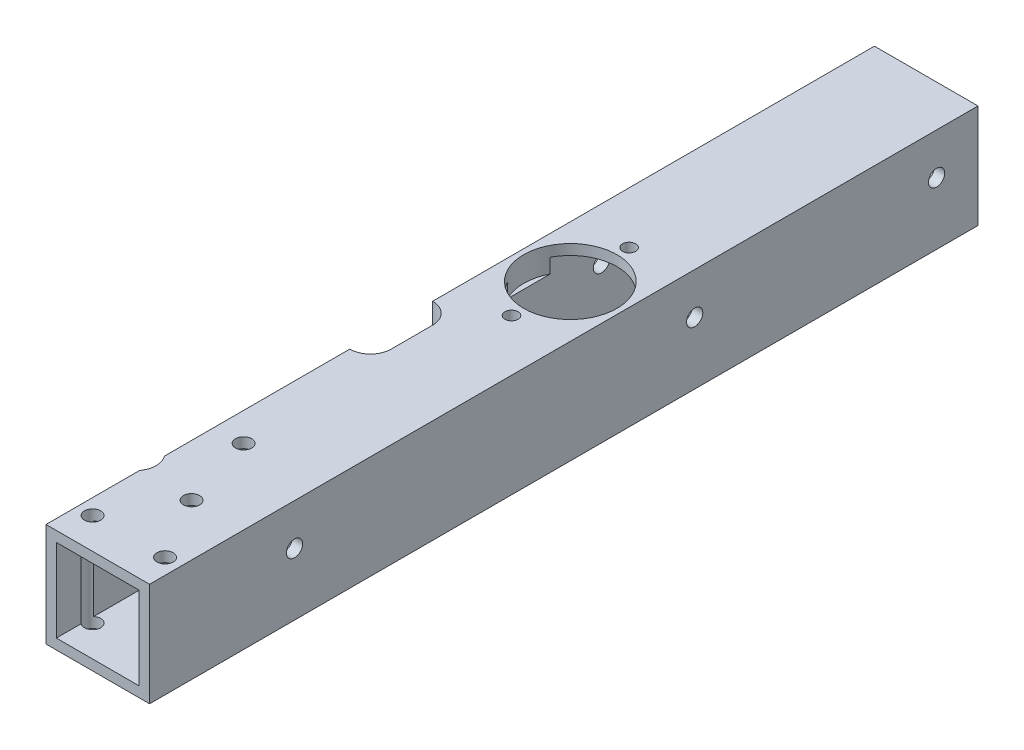
SolidWorks part; units mm, degrees
material "6061 Alloy"
ref_plane "Front Plane" through (0, 0, 0) normal (0, 0, 1) x (1, 0, 0)
ref_plane "Top Plane" through (0, 0, 0) normal (0, 1, 0) x (1, 0, 0)
ref_plane "Right Plane" through (0, 0, 0) normal (1, 0, 0) x (0, 0, -1)
sketch "Sketch1" plane through (0, 0, 0) normal (0, 0, 1) x (1, 0, 0)
  line L0 (-12.7, 12.7) -> (12.7, 12.7)
  line L2 (-15.875, 15.875) -> (15.875, 15.875)
  line L3 (-15.875, 15.875) -> (-15.875, -15.875)
  line L4 (-15.875, -15.875) -> (15.875, -15.875)
  line L5 (15.875, 15.875) -> (15.875, -15.875)
  line L10 (12.7, 12.7) -> (12.7, -12.7)
  line L11 (-12.7, -12.7) -> (12.7, -12.7)
  line L12 (-12.7, 12.7) -> (-12.7, -12.7)
  point P12 (0, 15.875)
  point P14 (15.875, 0)
  dimension "Wall Thickness" = 3.175
  dimension "Outside Width" = 31.75
  dimension "Outside Height" = 31.75
  dimension "Inside Height" = 25.4
  dimension "Inside Width" = 25.4
sketch "Sketch2" plane through (0, 0, 0) normal (1, 0, 0) x (0, 0, -1)
  line L0 (127, 0) -> (-127, 0)
  point P4 (0, 0)
  point P7 (-127, 0)
  point P10 (127, 0)
  dimension "Length" = 254
sketch "Sketch3" plane through (0, 0, 0) normal (0, 0, 1) x (1, 0, 0)
  line L21 (15.875, 15.875) -> (-15.875, 15.875)
  line L22 (15.875, -15.875) -> (15.875, 15.875)
  line L23 (-15.875, -15.875) -> (15.875, -15.875)
  line L24 (-15.875, 15.875) -> (-15.875, -15.875)
  line L25 (15.875, 15.875) -> (-15.875, 15.875)
  line L26 (15.875, -15.875) -> (15.875, 15.875)
  line L27 (-15.875, -15.875) -> (15.875, -15.875)
  line L28 (-15.875, 15.875) -> (-15.875, -15.875)
  line L29 (12.7, 12.7) -> (-12.7, 12.7)
  line L30 (12.7, -12.7) -> (12.7, 12.7)
  line L31 (-12.7, -12.7) -> (12.7, -12.7)
  line L32 (-12.7, 12.7) -> (-12.7, -12.7)
  line L33 (12.7, 12.7) -> (-12.7, 12.7)
  line L34 (12.7, -12.7) -> (12.7, 12.7)
  line L35 (-12.7, -12.7) -> (12.7, -12.7)
  line L36 (-12.7, 12.7) -> (-12.7, -12.7)
  dimension "D1" = 0
  dimension "D2" = 0
extrude "Boss-Extrude1" add sketch "Sketch3" along normal up to vertex (127 mm away) and the other way up to vertex (127 mm away) up to point (0, 0, 127) other way up to point (0, 0, -127)
sketch "Drawing Reference" plane through (0, 0, 0) normal (1, 0, 0) x (0, 0, -1)
  line L0 (-127, 0) -> (127, 0) construction
  line L1 (0, -15.875) -> (0, 15.875) construction
  line L2 (-127, -15.875) -> (127, -15.875) construction
  line L5 (-127, 15.875) -> (127, 15.875) construction
  point P7 (-104.14, 0)
  point P8 (104.14, 0)
  dimension "D1" = 22.86
sketch "Sketch4" plane through (0, 15.875, 0) normal (0, 1, 0) x (1, 0, 0)
  line L0 (0, -127) -> (0, -117.475) construction
  line L1 (15.875, -127) -> (-15.875, -127) construction
  line L2 (0, -117.475) -> (11.1125, -117.475) construction
  line L3 (0, -117.475) -> (-11.1125, -117.475) construction
  line L4 (0, -117.475) -> (0, 17.8816) construction
  line L5 (0, -117.475) -> (0, -98.2472) construction
  point P5 (-7.1119, -75.1713)
  dimension "D1" = 135.3566
  dimension "D2" = 22.225
  dimension "D3" = 9.525
hole_wizard "#10 Clearance Hole1" positions "Sketch5" profile "Sketch6" hole size "#10" standard "ANSI Inch" end condition through all
sketch "Sketch5" plane through (0, 15.875, 0) normal (0, 1, 0) x (1, 0, 0)
  point P0 (-11.1125, -117.475)
  point P3 (11.1125, -117.475)
  point P7 (0, -98.2472)
  point P10 (-7.1119, -75.1713)
sketch "Sketch6" plane through (-11.1125, 15.875, 117.475) normal (1, 0, 0) x (0, 0, 1)
  line L0 (0, 0) -> (0, 31.75)
  line L1 (0, 31.75) -> (2.4892, 31.75)
  line L2 (2.4892, 31.75) -> (2.4892, 0)
  line L5 (2.4892, 0) -> (0, 0)
  line L11 (0, -6.35) -> (0, 107.95) construction
  dimension "Thru Hole Dia." = 4.9784
  dimension "Thru Hole Depth" = 31.75
sketch "Sketch7" plane through (0, 15.875, 0) normal (0, 1, 0) x (1, 0, 0)
  circle A0 centre (0, 17.8816) radius 14.2875
  dimension "D1" = 28.575
extrude "Cut-Extrude1" cut sketch "Sketch7" against normal blind 7.62
sketch "Sketch8" plane through (0, -15.875, 0) normal (0, -1, 0) x (1, 0, 0)
  circle A0 centre (0, -17.8816) radius 14.2875
  dimension "D1" = 28.575
extrude "Cut-Extrude2" cut sketch "Sketch8" against normal blind 7.62
sketch "Sketch9" plane through (0, -15.875, 0) normal (0, -1, 0) x (1, 0, 0)
  line L0 (-20.5727, 87.7258) -> (-42.1132, 74.2659) construction
  line L1 (-42.1132, 74.2659) -> (-15.875, 32.276) construction
  line L2 (-15.875, 127) -> (-15.875, -127) construction
  line L3 (-15.875, 32.276) -> (-9.099, 21.4322) construction
  line L4 (-15.875, 32.276) -> (-15.875, 27.5135) construction
  line L5 (-15.875, 27.5135) -> (-15.875, 14.8135) construction
  line L6 (-9.525, 27.5135) -> (-9.525, 14.8135)
  line L7 (-15.875, 8.4635) -> (-15.875, 33.8635)
  circle A0 centre (-15.875, 27.5135) radius 6.35 construction
  circle A1 centre (-15.875, 14.8135) radius 6.35 construction
  arc A2 (-15.875, 33.8635) -> (-9.525, 27.5135) centre (-15.875, 27.5135) cw
  arc A3 (-15.875, 8.4635) -> (-9.525, 14.8135) centre (-15.875, 14.8135) ccw
  dimension "D1" = 12.7
  dimension "D2" = 4.7625
extrude "Cut-Extrude3" cut sketch "Sketch9" against normal through all
sketch "Sketch10" plane through (15.875, 0, 0) normal (1, 0, 0) x (0, 0, -1)
  line L0 (-127, 3.175) -> (-82.55, 3.175) construction
  line L2 (-82.55, 3.175) -> (114.3, 3.175) construction
  line L3 (-127, -15.875) -> (-127, 3.175) construction
  line L4 (52.832, 3.175) -> (40.132, 3.175) construction
  line L5 (52.832, 434.0225) -> (52.832, -10.4775) construction
  dimension "D1" = 44.45
  dimension "D2" = 19.05
  dimension "D3" = 12.7
hole_wizard "#10 Clearance Hole2" positions "Sketch11" profile "Sketch12" hole size "#10" standard "ANSI Inch" end condition through all
sketch "Sketch11" plane through (15.875, 0, 0) normal (1, 0, 0) x (0, 0, -1)
  point P4 (-82.55, 3.175)
  point P7 (114.3, 3.175)
  point P12 (40.132, 3.175)
sketch "Sketch12" plane through (15.875, 3.175, 82.55) normal (0, 1, 0) x (0, 0, -1)
  line L0 (0, 0) -> (0, 31.75)
  line L1 (0, 31.75) -> (2.4892, 31.75)
  line L2 (2.4892, 31.75) -> (2.4892, 0)
  line L5 (2.4892, 0) -> (0, 0)
  line L11 (0, -6.35) -> (0, 107.95) construction
  dimension "Thru Hole Dia." = 4.9784
  dimension "Thru Hole Depth" = 31.75
sketch "Sketch13" plane through (0, -15.875, 0) normal (0, -1, 0) x (1, 0, 0)
  line L0 (-20.955, 94.5257) -> (-15.875, 94.5257) construction
  line L4 (-15.875, 127) -> (-15.875, 33.8635) construction
  circle A1 centre (-20.955, 94.5257) radius 6.35
  dimension "D1" = 5.08
extrude "Cut-Extrude4" cut sketch "Sketch13" against normal through all
sketch "Sketch14" plane through (0, -15.875, 0) normal (0, -1, 0) x (1, 0, 0)
  line L0 (0, -35.9156) -> (0, 0.1524) construction
  line L1 (0, 117.475) -> (0, -17.8816) construction
  line L2 (0, -17.8816) -> (5.4169, -17.8816) construction
  point P7 (0, -17.8816)
  dimension "D1" = 36.068
hole_wizard "Tap Drill for #10-32 Tap2" positions "Sketch17" profile "Sketch18" hole size "#10-32" standard "ANSI Inch"
sketch "Sketch17" plane through (0, 15.875, 0) normal (0, 1, 0) x (1, 0, 0)
  point P4 (0, 35.9156)
  point P9 (0, -0.1524)
sketch "Sketch18" plane through (0, 15.875, -35.9156) normal (1, 0, 0) x (0, 0, 1)
  line L0 (0, 0) -> (0, 6.2933)
  line L1 (0, 6.2933) -> (2.0193, 5.08)
  line L2 (2.0193, 5.08) -> (2.0193, 0)
  line L5 (2.0193, 0) -> (0, 0)
  line L10 (0, 6.2933) -> (-2.0193, 5.08) construction
  line L11 (0, -6.35) -> (0, 107.95) construction
  dimension "Hole Dia." = 4.0386
  dimension "Hole Depth" = 5.08
  dimension "Drill Angle" = 118
equation "\"D1@Drawing Reference\"=\"Outside Width@Sketch1\" * 0.72"
